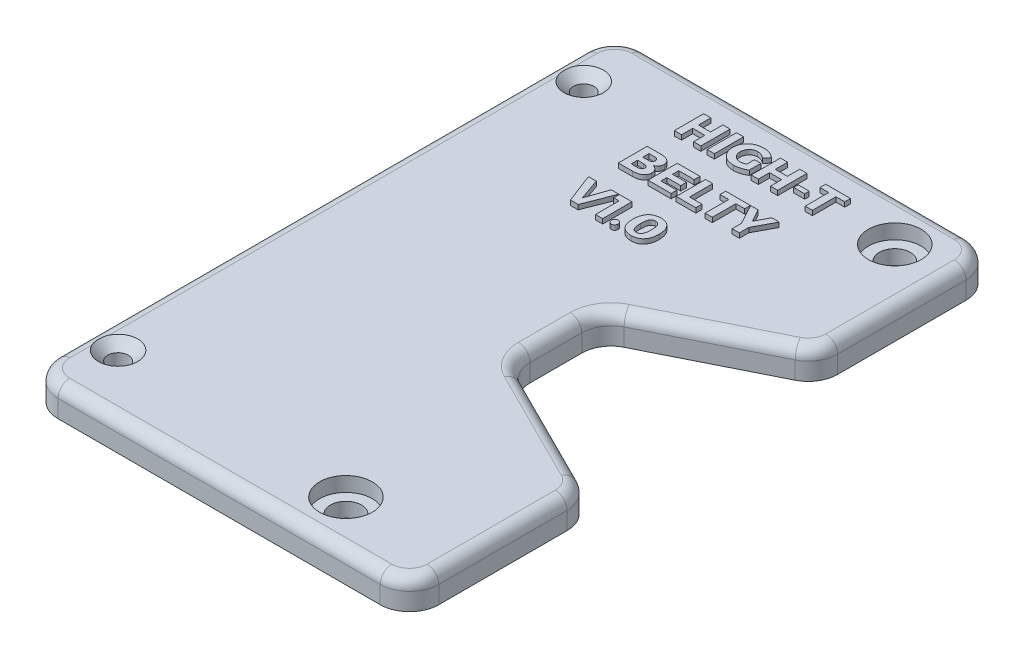
SolidWorks part; units mm, degrees
ref_plane "Front Plane" through (0, 0, 0) normal (0, 0, 1) x (1, 0, 0)
ref_plane "Top Plane" through (0, 0, 0) normal (0, 1, 0) x (1, 0, 0)
ref_plane "Right Plane" through (0, 0, 0) normal (1, 0, 0) x (0, 0, -1)
sketch "Sketch2" plane through (0, 0, 0) normal (0, 1, 0) x (1, 0, 0)
  line L1 (-32.5, 50) -> (32.5, 50)
  line L2 (-32.5, 50) -> (-32.5, -50)
  line L3 (-32.5, -50) -> (32.5, -50)
  line L4 (32.5, 50) -> (32.5, -50)
  line L5 (-32.5, 50) -> (32.5, -50) construction
  line L6 (-32.5, -50) -> (32.5, 50) construction
  circle A0 centre (-27.5, 39.75) radius 1.75
  circle A1 centre (-27.5, -39.75) radius 1.75
  circle A2 centre (23.15, 42.205) radius 2.65
  circle A3 centre (13.65, -42) radius 2.65
  circle A4 centre (23.15, 42.205) radius 3.5 construction
  circle A5 centre (13.65, -42) radius 3.5 construction
  point P0 (0, 0)
  dimension "D3" = 3.5
  dimension "D4" = 5
  dimension "D8" = 5.3
  dimension "D1" = 65
  dimension "D2" = 100
  dimension "D5" = 5
  dimension "D6" = 10.25
  dimension "D7" = 10.25
extrude "Boss-Extrude1" add sketch "Sketch2" along normal blind 5
sketch "Sketch3" plane through (0, 5, 0) normal (0, 1, 0) x (1, 0, 0)
  circle A0 centre (23.15, 42.205) radius 4.5
  circle A1 centre (13.65, -42) radius 4.5
  dimension "D1" = 9
  dimension "D2" = 9
extrude "Cut-Extrude1" cut sketch "Sketch3" against normal blind 2.5
fillet "Fillet1" radius 5 4 edges at (-32.5, 2.5, 50) (-32.5, 2.5, -50) (32.5, 2.5, -50) (32.5, 2.5, 50)
chamfer "Chamfer1" distance 1.6 angle 45 2 edges at (-27.5, 5, 41.5) (-27.5, 5, -38)
sketch "Sketch6" plane through (0, 5, 0) normal (0, 1, 0) x (1, 0, 0)
  line L0 (7.5, 7.5) -> (32.5, 20)
  line L1 (32.5, -45) -> (32.5, 45) construction
  line L2 (32.5, 20) -> (32.5, -20)
  line L3 (32.5, -20) -> (7.5, -7.5)
  line L4 (7.5, -7.5) -> (7.5, 7.5)
  point P4 (7.5, 0)
  dimension "D1" = 25
  dimension "D2" = 40
  dimension "D3" = 15
extrude "Cut-Extrude2" cut sketch "Sketch6" against normal through all
fillet "Fillet3" radius 5 4 edges at (32.5, 2.5, -20) (7.5, 2.5, -7.5) (7.5, 2.5, 7.5) (32.5, 2.5, 20)
fillet "Fillet2" radius 2 16 edges at (-31.0355, 5, 48.5355) (-32.5, 5, 0) (-31.0355, 5, -48.5355) (0, 5, -50) (31.0355, 5, -48.5355) (32.5, 5, -34.0451) (32.5, 5, 34.0451) (31.0355, 5, 48.5355) (0, 5, 50) (31.7533, 5, -20.4615) (20, 5, -13.75) (8.2467, 5, -7.0385) (7.5, 5, 0) (8.2467, 5, 7.0385) (20, 5, 13.75) (31.7533, 5, 20.4615)
sketch "Sketch4" plane through (0, 5, 0) normal (0, 1, 0) x (1, 0, 0)
  text T0 "<b>HIGH-T</b>\r\n<b>BELTY</b>\r\n<b>V1.0</b>" font "Montserrat" height 5
extrude "Boss-Extrude2" add sketch "Sketch4" along normal blind 0.8
